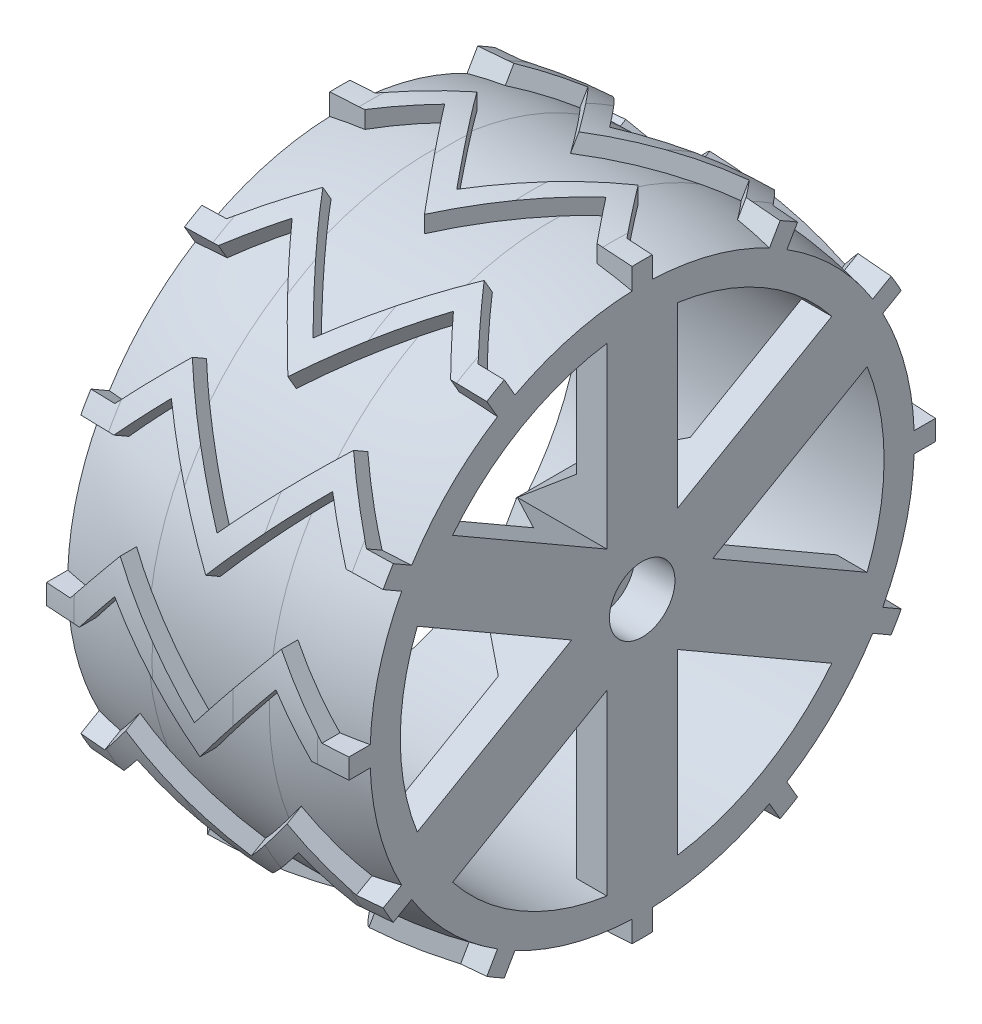
SolidWorks part; units mm, degrees
material "ABS"
ref_plane "Přední rovina" through (0, 0, 0) normal (0, 0, 1) x (1, 0, 0)
ref_plane "Horní rovina" through (0, 0, 0) normal (0, 1, 0) x (1, 0, 0)
ref_plane "Pravá rovina" through (0, 0, 0) normal (1, 0, 0) x (0, 0, -1)
sketch "Skica1" plane through (0, 0, 0) normal (0, 0, 1) x (1, 0, 0)
  line L0 (0, 0) -> (-19.9482, 0) construction
  line L1 (0, 0) -> (0, 24) construction
  line L2 (15, 24) -> (-15, 24)
  line L3 (-15, 24) -> (-15, 27)
  line L4 (0, 24) -> (0, 28) construction
  line L5 (6, 28) -> (-6, 28)
  line L6 (15, 24) -> (15, 27)
  arc A0 (-15, 27) -> (-6, 28) centre (-6, -13) cw
  arc A1 (15, 27) -> (6, 28) centre (6, -13) ccw
  dimension "D1" = 56
  dimension "D2" = 15
  dimension "D3" = 3
  dimension "D4" = 4
  dimension "D5" = 6
revolve "Rotovat1" add sketch "Skica1" angle 360 about L0 other way angle 360
ref_plane "Rovina1" through (0, 30, 0) normal (0, 1, 0) x (1, 0, 0)
sketch "Skica3" plane through (0, 30, 0) normal (0, 1, 0) x (1, 0, 0)
  line L0 (-15, 0) -> (-12, 0)
  line L1 (-15, 27) -> (-15, -27) construction
  line L2 (-12, 0) -> (-8, 5)
  line L3 (-8, 5) -> (-4, 0)
  line L4 (0, 0) -> (-10.2838, 0) construction
  line L5 (0, 0) -> (0, -5) construction
  line L6 (-8, 5) -> (-8, 0) construction
  line L7 (-4, 0) -> (0, -5)
  line L8 (4, 0) -> (0, -5)
  line L9 (8, 5) -> (4, 0)
  line L10 (12, 0) -> (8, 5)
  line L11 (15, 0) -> (12, 0)
  dimension "D1" = 5
  dimension "D2" = 3
extrude "Vysunout tenkostěnný1" add sketch "Skica3" against normal blind 10 thin thin type mid plane wall 2
pattern_circular "Kruhové pole1" count 12 over 360 about axis through (0, 0, 0) along (1, 0, 0) of "Vysunout tenkostěnný1"
sketch "Skica4" plane through (0, 0, 0) normal (1, 0, 0) x (0, 0, -1)
  circle A0 centre (0, 0) radius 24
  circle A1 centre (0, 0) radius 27
  circle A2 centre (0, 0) radius 24 construction
  dimension "D1" = 3
extrude "Odebrat vysunutím2" cut sketch "Skica4" against normal mid plane 30 contours A0 region at (0, 0, 0)
sketch "Skica5" plane through (0, 0, 0) normal (1, 0, 0) x (0, 0, -1)
  circle A0 centre (0, 0) radius 30
  circle A1 centre (0, 0) radius 24 construction
  circle A2 centre (0, 0) radius 40
  dimension "D1" = 6
  dimension "D2" = 10
extrude "Odebrat vysunutím3" cut sketch "Skica5" against normal mid plane 30
sketch "Skica6" plane through (0, 0, 0) normal (0, 0, 1) x (1, 0, 0)
  line L0 (-15, 26.9815) -> (-15, 29.9833) construction
  line L1 (-2, 28.618) -> (-4, 28.618) construction
  line L2 (-2, 28.618) -> (4, 28.618) construction
  line L3 (-2, 29.618) -> (4, 29.618)
  line L4 (-2, 29.618) -> (-4, 29.618)
  line L5 (-15, 29.113) -> (-18.0891, 33.8325)
  line L6 (-18.0891, 33.8325) -> (1.0133, 32.6178)
  line L7 (1.0133, 32.6178) -> (17.1086, 33.5822)
  line L8 (17.1086, 33.5822) -> (15, 29.113)
  line L9 (0, 0) -> (-14.4667, 0) construction
  line L10 (15, 26.9815) -> (15, 29.9833) construction
  arc A4 (-12, 28.2983) -> (-14, 28.118) centre (-4, -71.632) ccw construction
  arc A5 (-4, 28.618) -> (-12, 28.2983) centre (-4, -71.632) ccw construction
  arc A6 (14, 28.118) -> (12, 28.2983) centre (4, -71.632) ccw construction
  arc A7 (12, 28.2983) -> (4, 28.618) centre (4, -71.632) ccw construction
  arc A8 (15, 29.113) -> (12.0798, 29.2951) centre (7.2394, -71.8391) ccw
  arc A9 (12.0798, 29.2951) -> (4, 29.618) centre (4, -71.632) ccw
  arc A10 (-4, 29.618) -> (-12.0798, 29.2951) centre (-4, -71.632) ccw
  arc A11 (-12.0798, 29.2951) -> (-15, 29.113) centre (-7.2394, -71.8391) ccw
revolve "Odebrat rotací1" cut sketch "Skica6" angle 360 about L9 region at (-0.4869, 31.3717, 0)
sketch "Skica7" plane through (0, 0, 0) normal (0, 0, 1) x (1, 0, 0)
  line L0 (-6, 0) -> (-27.797, 0) construction
  line L1 (-15, 24) -> (-15, 13)
  line L2 (-15, 12.6247) -> (-15, 1) construction
  line L4 (-15, 13) -> (-15, 0)
  line L5 (-15, 0) -> (-6, 0)
  line L6 (-6, 0) -> (-6, 5.9654)
  line L7 (-6, 5.9654) -> (-12, 11)
  line L8 (-12, 11) -> (-12, 24)
  line L9 (-12, 24) -> (-15, 24)
  line L10 (-15, -1) -> (-15, -12.6247) construction
  dimension "D1" = 3
  dimension "D2" = 13
  dimension "D3" = 9
  dimension "D4" = 130
  dimension "D5" = 11
extrude "Přidat vysunutím1" add sketch "Skica7" along normal mid plane 7
pattern_circular "Kruhové pole2" count 6 over 360 of "Přidat vysunutím1"
sketch "Skica9" plane through (-15, 0, 0) normal (-1, 0, 0) x (0, 0, 1)
  circle A0 centre (0, 0) radius 3.25
  dimension "D1" = 6.5
extrude "Odebrat vysunutím4" cut sketch "Skica9" against normal blind 4
sketch "Skica10" plane through (-11, 0, 0) normal (-1, 0, 0) x (0, 0, 1)
  circle A0 centre (0, 0) radius 1.4
  dimension "D1" = 2.8
extrude "Odebrat vysunutím5" cut sketch "Skica10" against normal blind 12
sketch "Skica11" plane through (-6, 0, 0) normal (1, 0, 0) x (0, 0, -1)
  circle A0 centre (0, 0) radius 2.75
  dimension "D1" = 5.5
extrude "Odebrat vysunutím6" [suppressed] cut sketch "Skica11" against normal blind 2.5
sketch "Skica12" plane through (-6, 0, 0) normal (1, 0, 0) x (0, 0, -1)
  line L24 (-3.4441, 5.9654) -> (-3.5, 5.9654)
  line L25 (-3.4441, 5.9654) -> (-3.5, 5.9654)
  line L26 (-6.8883, 0) -> (-6.9162, -0.0484)
  line L27 (-6.8883, 0) -> (-6.9162, -0.0484)
  line L28 (-3.4441, -5.9654) -> (-3.4162, -6.0138)
  line L29 (-3.4441, -5.9654) -> (-3.4162, -6.0138)
  line L30 (3.4441, -5.9654) -> (3.5, -5.9654)
  line L31 (-3.3324, 5.9654) -> (-3.4162, 6.0138)
  line L32 (-3.4162, 6.0138) -> (-3.4441, 5.9654)
  line L33 (3.4441, -5.9654) -> (3.5, -5.9654)
  line L34 (-3.5, 5.9654) -> (-3.5, 5.8686)
  line L35 (6.8883, 0) -> (6.9162, 0.0484)
  line L36 (-6.8324, 0.0968) -> (-6.9162, 0.0484)
  line L37 (-6.9162, 0.0484) -> (-6.8883, 0)
  line L38 (6.8883, 0) -> (6.9162, 0.0484)
  line L39 (-6.9162, -0.0484) -> (-6.8324, -0.0968)
  line L40 (3.5, 5.9654) -> (3.4441, 5.9654)
  line L41 (-3.5, -5.8686) -> (-3.5, -5.9654)
  line L42 (-3.5, -5.9654) -> (-3.4441, -5.9654)
  line L43 (3.5, 5.9654) -> (3.4441, 5.9654)
  line L44 (-3.4162, -6.0138) -> (-3.3324, -5.9654)
  line L45 (3.4441, 5.9654) -> (3.4162, 6.0138)
  line L46 (3.3324, -5.9654) -> (3.4162, -6.0138)
  line L47 (3.4162, -6.0138) -> (3.4441, -5.9654)
  line L48 (3.4441, 5.9654) -> (3.4162, 6.0138)
  line L49 (3.5, -5.9654) -> (3.5, -5.8686)
  line L51 (6.8324, -0.0968) -> (6.9162, -0.0484)
  line L52 (6.9162, -0.0484) -> (6.8883, 0)
  line L54 (6.9162, 0.0484) -> (6.8324, 0.0968)
  line L56 (3.5, 5.8686) -> (3.5, 5.9654)
  line L59 (3.4162, 6.0138) -> (3.3324, 5.9654)
  line L61 (-3.3324, 5.9654) -> (-3.4162, 6.0138)
  line L62 (-3.4162, 6.0138) -> (-3.4441, 5.9654)
  line L63 (3.3324, 5.9654) -> (-3.3324, 5.9654)
  line L64 (-3.5, 5.9654) -> (-3.5, 5.8686)
  line L65 (3.3324, 5.9654) -> (-3.3324, 5.9654)
  line L66 (-6.8324, 0.0968) -> (-6.9162, 0.0484)
  line L67 (-6.9162, 0.0484) -> (-6.8883, 0)
  line L68 (-3.5, 5.8686) -> (-6.8324, 0.0968)
  line L69 (-6.9162, -0.0484) -> (-6.8324, -0.0968)
  line L70 (-3.5, 5.8686) -> (-6.8324, 0.0968)
  line L71 (-3.5, -5.8686) -> (-3.5, -5.9654)
  line L72 (-3.5, -5.9654) -> (-3.4441, -5.9654)
  line L73 (-6.8324, -0.0968) -> (-3.5, -5.8686)
  line L74 (-3.4162, -6.0138) -> (-3.3324, -5.9654)
  line L75 (-6.8324, -0.0968) -> (-3.5, -5.8686)
  line L76 (3.3324, -5.9654) -> (3.4162, -6.0138)
  line L77 (3.4162, -6.0138) -> (3.4441, -5.9654)
  line L78 (-3.3324, -5.9654) -> (3.3324, -5.9654)
  line L79 (3.5, -5.9654) -> (3.5, -5.8686)
  line L80 (-3.3324, -5.9654) -> (3.3324, -5.9654)
  line L81 (6.8324, -0.0968) -> (6.9162, -0.0484)
  line L82 (6.9162, -0.0484) -> (6.8883, 0)
  line L83 (3.5, -5.8686) -> (6.8324, -0.0968)
  line L84 (6.9162, 0.0484) -> (6.8324, 0.0968)
  line L85 (3.5, -5.8686) -> (6.8324, -0.0968)
  line L86 (3.5, 5.8686) -> (3.5, 5.9654)
  line L87 (6.8324, 0.0968) -> (3.5, 5.8686)
  line L88 (6.8324, 0.0968) -> (3.5, 5.8686)
  line L89 (3.4162, 6.0138) -> (3.3324, 5.9654)
  circle A0 centre (0, 0) radius 7
  dimension "D1" = 0
extrude "Přidat vysunutím2" [suppressed] add sketch "Skica12" against normal up to next
sketch "Skica13" plane through (-6, 0, 0) normal (1, 0, 0) x (0, 0, -1)
  circle A0 centre (0, 0) radius 3.25
  dimension "D1" = 6.5
extrude "Odebrat vysunutím7" cut sketch "Skica13" against normal blind 2
mirror "Zrcadlit1" of bodies 144
delete or keep bodies "Tělo-Odstranit1" type delete bodies bodies 144
